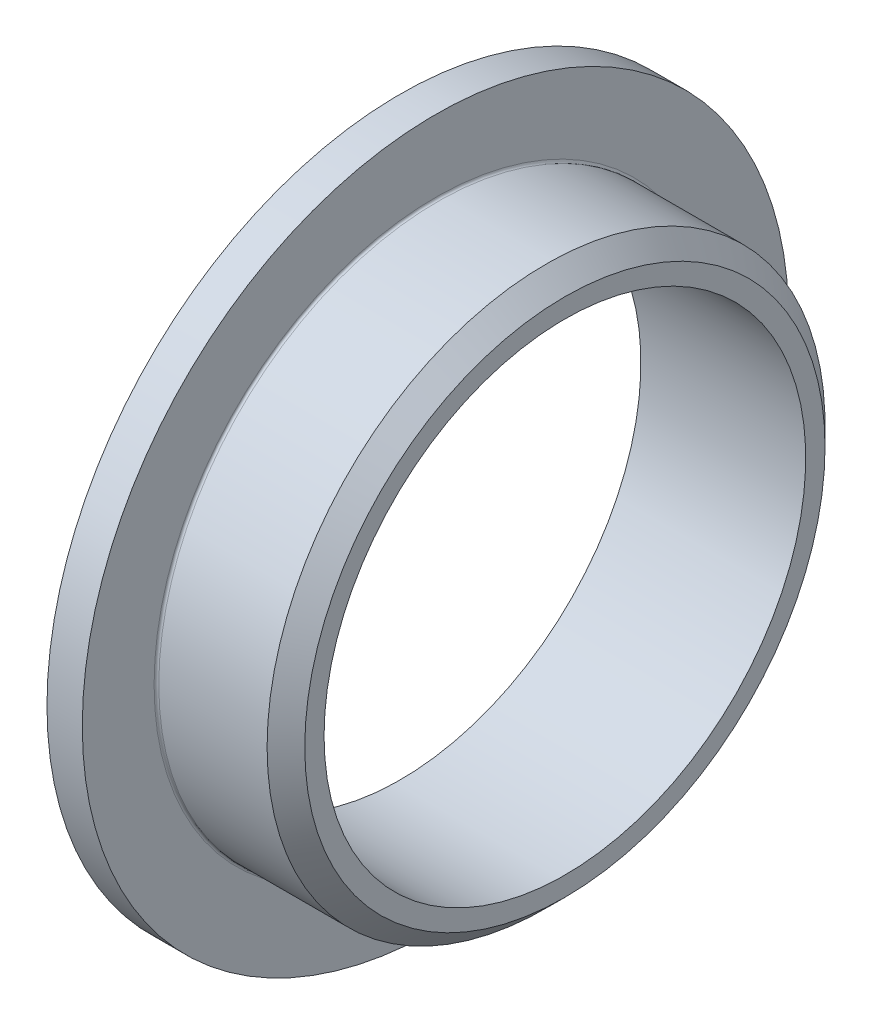
SolidWorks part; units mm, degrees
material "PPS"
ref_plane "Front Plane" through (0, 0, 0) normal (0, 0, 1) x (1, 0, 0)
ref_plane "Top Plane" through (0, 0, 0) normal (0, 1, 0) x (1, 0, 0)
ref_plane "Right Plane" through (0, 0, 0) normal (1, 0, 0) x (0, 0, -1)
sketch "Sketch1" plane through (0, 0, 0) normal (0, 0, 1) x (1, 0, 0)
  line L0 (0, 0) -> (22.3478, 0) construction
  line L1 (7, 10.23) -> (0, 10.23)
  line L2 (0, 10.23) -> (0, 15)
  line L3 (0, 15) -> (1.5, 15)
  line L4 (1.5, 15) -> (1.5, 11.85)
  line L5 (1.5, 11.85) -> (7, 11.85)
  line L6 (7, 11.85) -> (7, 10.23)
  point P9 (0, 12.615)
  dimension "D1" = 10.23
  dimension "D2" = 11.85
  dimension "D3" = 15
  dimension "D4" = 7
  dimension "D5" = 1.5
revolve "Revolve1" add sketch "Sketch1" angle 360 about L0
fillet "Fillet1" radius 0.1 1 edges at (1.5, 0, 11.85)
chamfer "Chamfer1" distance 0.8 angle 45 1 edges at (7, 0, 11.85)
